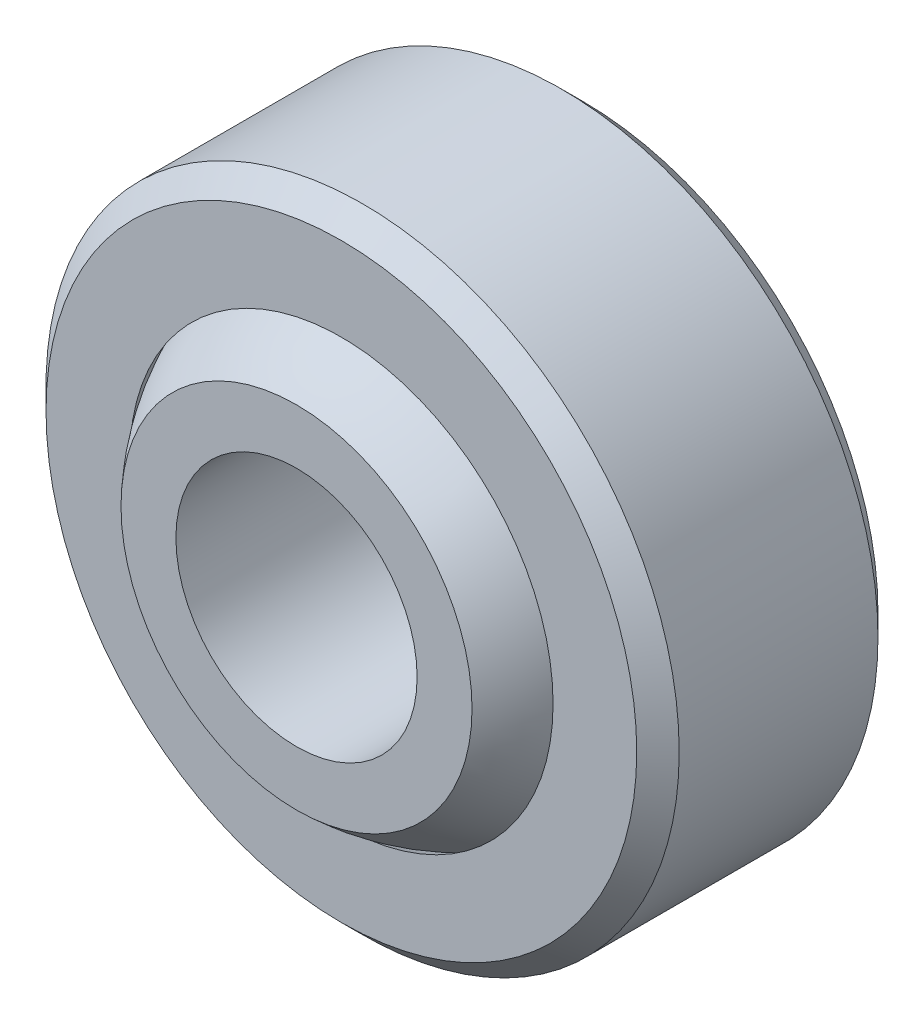
SolidWorks part; units mm, degrees
ref_plane "Front" through (0, 0, 0) normal (0, 0, 1) x (1, 0, 0)
ref_plane "Top" through (0, 0, 0) normal (0, 1, 0) x (1, 0, 0)
ref_plane "Right" through (0, 0, 0) normal (1, 0, 0) x (0, 0, -1)
sketch "Sketch1" plane through (0, 0, 0) normal (0, 0, 1) x (1, 0, 0)
  circle A0 centre (0, 0) radius 3.175 construction
  circle A1 centre (0, 0) radius 6.35 construction
  circle A2 centre (0, 0) radius 6.4135 construction
  circle A3 centre (0, 0) radius 8.3337
  dimension "D OD" = 16.6675
  dimension "B Hole Dia" = 6.35
  dimension "Ball Dia" = 12.7
  dimension "D1" = 12.827
extrude "Extrude1" add sketch "Sketch1" along normal mid plane 6.35
sketch "Sketch2" plane through (0, 0, 0) normal (0, 0, 1) x (1, 0, 0)
  line L0 (0, 6.4135) -> (0, -6.4135)
  line L1 (0, 6.4135) -> (0, 8.3337) construction
  circle A0 centre (0, 0) radius 6.4135 construction
  arc A1 (0, -6.4135) -> (0, 6.4135) centre (0, 0) ccw
  circle A2 centre (0, 0) radius 8.3337 construction
revolve "Cut-Revolve1" cut sketch "Sketch2" angle 360 about L1
sketch "Sketch3" plane through (0, 0, 0) normal (0, 0, 1) x (1, 0, 0)
  line L0 (0, 6.35) -> (0, -6.35)
  line L1 (0, 6.35) -> (0, 8.3337) construction
  circle A0 centre (0, 0) radius 6.35 construction
  arc A1 (0, -6.35) -> (0, 6.35) centre (0, 0) ccw
  circle A2 centre (0, 0) radius 8.3337 construction
revolve "Revolve1" add sketch "Sketch3" angle 360 about L1
sketch "Sketch4" plane through (0, 0, 0) normal (0, 0, 1) x (1, 0, 0)
  circle A0 centre (0, 0) radius 3.175 construction
  circle A1 centre (0, 0) radius 3.175
extrude "Cut-Extrude1" cut sketch "Sketch4" against normal through all and the other way through all
sketch "Sketch5" plane through (0, 0, 0) normal (1, 0, 0) x (0, 0, -1)
  line L0 (-4.3561, 8.3337) -> (4.3561, 8.3337) construction
  line L1 (-4.3561, 8.3337) -> (-5.4993, 8.3337)
  line L2 (-4.3561, 8.3337) -> (-4.3561, -8.3337)
  line L3 (-4.3561, -8.3337) -> (-5.4993, -8.3337)
  line L4 (-5.4993, 8.3337) -> (-5.4993, -8.3337)
  line L5 (4.3561, -8.3337) -> (5.4993, -8.3337)
  line L6 (4.3561, -8.3337) -> (4.3561, 8.3337)
  line L7 (4.3561, 8.3337) -> (5.4993, 8.3337)
  line L8 (5.4993, -8.3337) -> (5.4993, 8.3337)
  line L16 (3.175, 8.3337) -> (-3.175, 8.3337) construction
  line L17 (5.4993, -3.175) -> (5.4993, 3.175) construction
  line L18 (-5.4993, -3.175) -> (-5.4993, 3.175) construction
  line L19 (-4.3561, -8.3337) -> (4.3561, -8.3337) construction
  line L20 (-3.175, -8.3337) -> (3.175, -8.3337) construction
  line L21 (0, 0) -> (-4.3561, 1.0458) construction
  line L22 (0, 0) -> (-4.3561, -1.0458) construction
  dimension "W ball Width" = 8.7122
  dimension "Mis Angle" = 27
extrude "Cut-Extrude2" cut sketch "Sketch5" against normal through all and the other way through all
chamfer "Chamfer1" distance 0.5588 angle 45 2 edges at (8.3337, 0, 3.175) (8.3337, 0, -3.175)
sketch "Sketch7" plane through (0, 0, 0) normal (1, 0, 0) x (0, 0, -1)
  line L0 (0, 0) -> (-4.3561, -1.0458) construction
  line L1 (0, 0) -> (-4.3561, 1.0458) construction
  line L2 (0, 0) -> (-4.3561, -1.0458) construction
  line L3 (0, 0) -> (-4.3561, 1.0458) construction
  line L4 (4.3561, 3.175) -> (-4.3561, 3.175)
  line L5 (-4.3561, -3.175) -> (4.3561, -3.175)
  line L6 (-4.3561, -3.175) -> (4.3561, -3.175) construction
  line L7 (4.3561, 3.175) -> (-4.3561, 3.175) construction
  arc A0 (3.175, 5.5725) -> (-3.175, 5.5725) centre (0, 0) ccw
  arc A1 (-3.175, -5.5725) -> (3.175, -5.5725) centre (0, 0) ccw
  arc A2 (-3.175, -5.5725) -> (3.175, -5.5725) centre (0, 0) ccw construction
  arc A3 (3.175, 5.5725) -> (-3.175, 5.5725) centre (0, 0) ccw construction
ref_axis "Center Axis 1" through (0, 0, -3.9256) along (0, 0, 1)
ref_plane "Contact Plane 1" through (0, 0, 4.3561) normal (0, 0, 1) x (1, 0, 0)
ref_plane "Contact Plane 2" through (0, 0, -4.3561) normal (0, 0, -1) x (-1, 0, 0)
sketch "Sketch8" plane through (0, 0, 0) normal (1, 0, 0) x (0, 0, -1)
  line L0 (3.175, 8.3337) -> (7.4623, 8.3337)
  line L1 (3.175, 6.8097) -> (7.4623, 6.8097)
  line L2 (3.175, 6.8097) -> (3.175, 8.3337)
  line L3 (3.175, -7.7749) -> (3.175, 7.7749) construction
  line L5 (2.6162, 8.3337) -> (7.4623, 8.3337) construction
  line L6 (2.6162, 6.8097) -> (7.4623, 6.8097) construction
  dimension "D1" = 1.524
sketch3d "3DSketch1"
  point P0 (0, 0, 0)
  point P1 (0, 0, 0)
equation "\"D1@Sketch1\"=\"Ball Dia@Sketch1\"*1.01"
